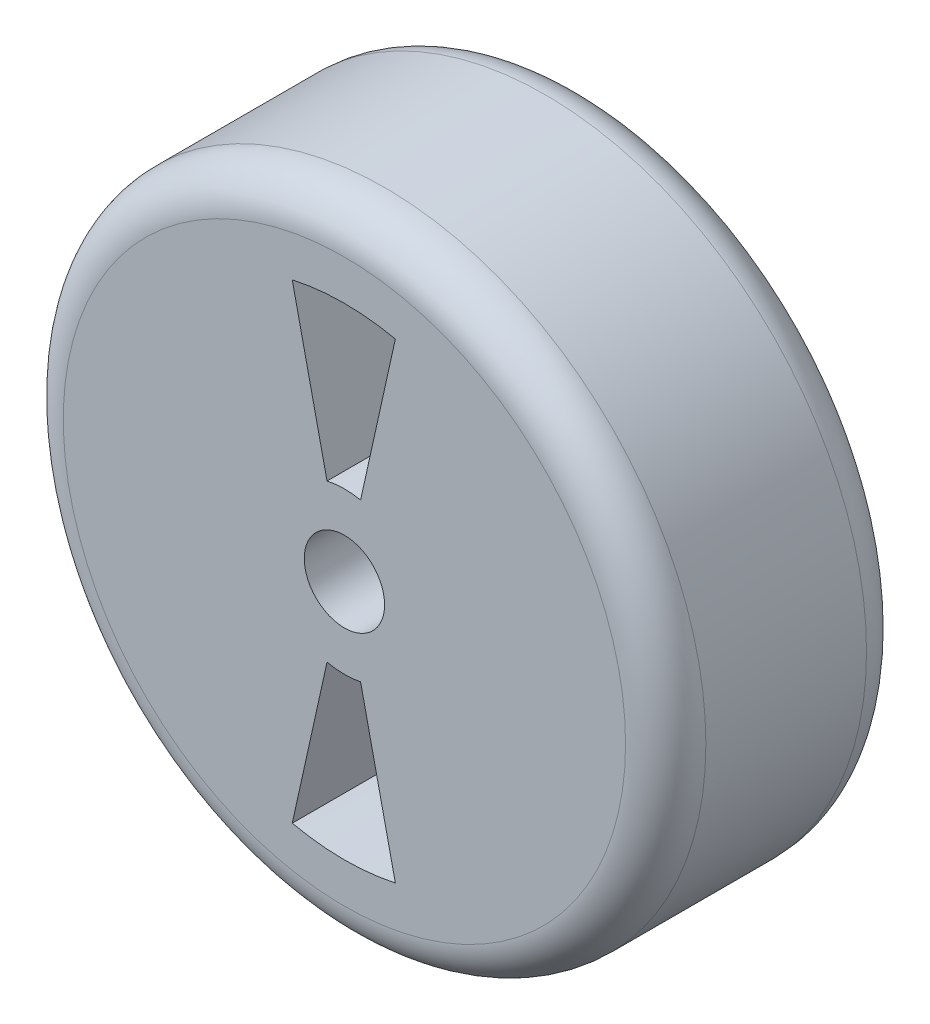
SolidWorks part; units mm, degrees
ref_plane "Front Plane" through (0, 0, 0) normal (0, 0, 1) x (1, 0, 0)
ref_plane "Top Plane" through (0, 0, 0) normal (0, 1, 0) x (1, 0, 0)
ref_plane "Right Plane" through (0, 0, 0) normal (1, 0, 0) x (0, 0, -1)
sketch "Sketch1" plane through (0, 0, 0) normal (0, 0, 1) x (1, 0, 0)
  circle A0 centre (0, 0) radius 101.6
extrude "Boss-Extrude1" add sketch "Sketch1" along normal blind 38.1 and the other way blind 38.1
sketch "Sketch2" plane through (0, 0, 38.1) normal (0, 0, 1) x (1, 0, 0)
  circle A0 centre (0, 0) radius 12.7
extrude "Cut-Extrude1" cut sketch "Sketch2" against normal through all
fillet "Fillet1" radius 12.7 1 edges at (101.6, 0, 38.1)
fillet "Fillet2" radius 12.7 1 edges at (101.6, 0, -38.1)
sketch "Sketch3" plane through (0, 0, 38.1) normal (0, 0, 1) x (1, 0, 0)
  line L1 (5.1106, 24.8806) -> (16.108, 74.4865)
  line L2 (-5.4976, 24.7979) -> (-16.4945, 74.4018)
  arc A0 (5.1106, 24.8806) -> (-5.4976, 24.7979) centre (0, 0) ccw
  arc A1 (16.108, 74.4865) -> (-16.4945, 74.4018) centre (0, 0) ccw
  dimension "D1" = 25
extrude "Cut-Extrude2" cut sketch "Sketch3" against normal through all
mirror "Mirror1" about plane through (0, 0, 0) normal (0, 1, 0) of "Cut-Extrude2"
ref_plane "Plane1" through (16.108, 74.4865, 38.1) normal (0.2164, 0.9763, 0) x (0.9763, -0.2164, 0)
